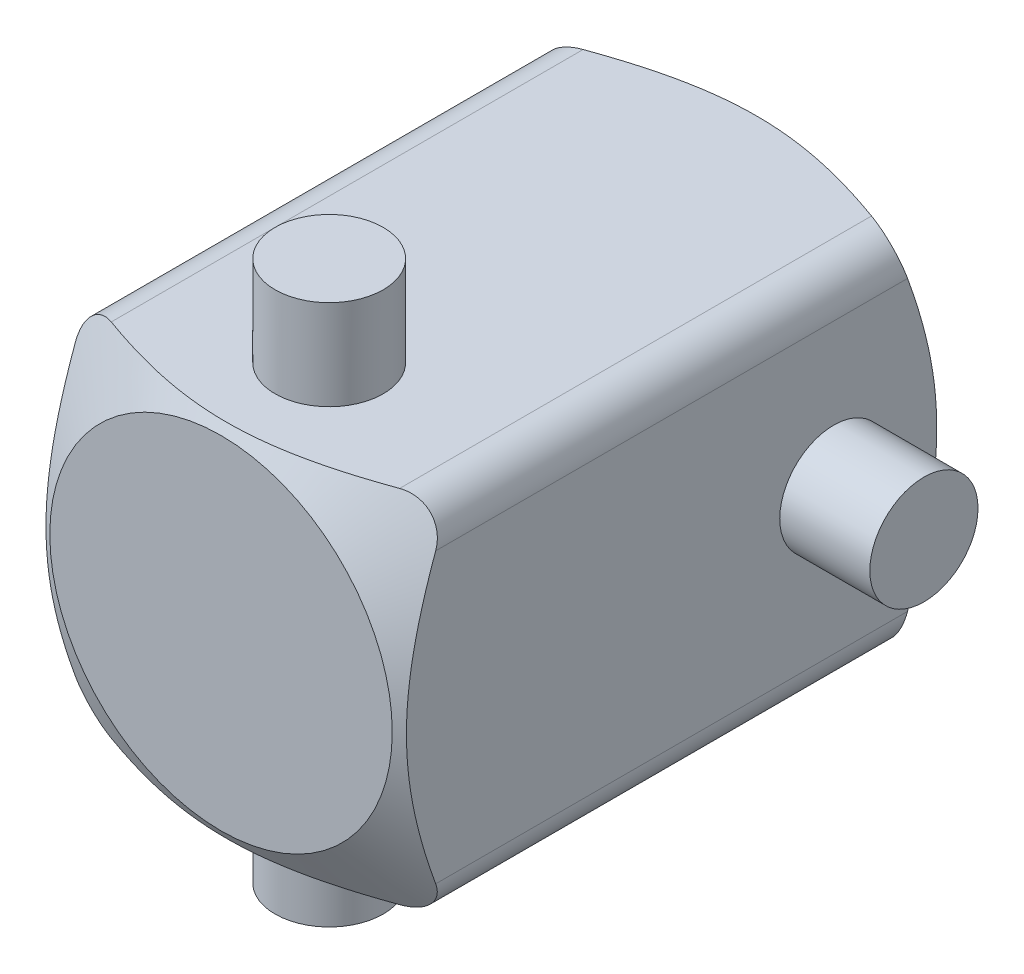
SolidWorks part; units mm, degrees
ref_plane "Alzado" through (0, 0, 0) normal (0, 0, 1) x (1, 0, 0)
ref_plane "Planta" through (0, 0, 0) normal (0, 1, 0) x (1, 0, 0)
ref_plane "Vista lateral" through (0, 0, 0) normal (1, 0, 0) x (0, 0, -1)
sketch "Croquis1" plane through (0, 0, 0) normal (0, 0, 1) x (1, 0, 0)
  line L1 (-5, 5) -> (5, 5)
  line L2 (-5, 5) -> (-5, -5)
  line L3 (-5, -5) -> (5, -5)
  line L4 (5, 5) -> (5, -5)
  line L5 (-5, 5) -> (5, -5) construction
  line L6 (-5, -5) -> (5, 5) construction
  point P0 (0, 0)
  dimension "D1" = 10
  dimension "D2" = 10
extrude "Saliente-Extruir1" add sketch "Croquis1" along normal blind 15
ref_axis "Eje1" through (0, 0, -0.75) along (0, 0, 1)
sketch "Croquis3" plane through (0, 0, 0) normal (1, 0, 0) x (0, 0, -1)
  line L0 (-15, 4.75) -> (-15, 15.04)
  line L1 (-15, -5) -> (-15, 5) construction
  line L2 (-15, 15.04) -> (0, 15.04)
  line L3 (0, 15.04) -> (0, 4.75)
  line L4 (0, -5) -> (0, 5) construction
  line L5 (0, 4.75) -> (-4.4745, 12.5)
  line L6 (-4.4745, 12.5) -> (-10.5255, 12.5)
  line L7 (-10.5255, 12.5) -> (-15, 4.75)
  line L8 (-15, 5) -> (0, 5) construction
  dimension "D1" = 0.25
  dimension "D2" = 0.25
  dimension "D3" = 2.54
  dimension "D4" = 30
  dimension "D5" = 30
  dimension "D6" = 7.5
revolve "Cortar-Revolución1" cut sketch "Croquis3" angle 360 about axis through (0, 0, -0.75) along (0, 0, 1)
fillet "Redondeo1" radius 1 4 edges at (-5, 5, 7.5) (-5, -5, 7.5) (5, -5, 7.5) (5, 5, 7.5)
sketch "Croquis4" plane through (0, 0, 0) normal (1, 0, 0) x (0, 0, -1)
  line L0 (0, -4.75) -> (0, 4.75) construction
  line L1 (0.75, 0) -> (-15.75, 0) construction
  circle A0 centre (-3, 0) radius 1.5
  point P4 (0, 0)
  dimension "D1" = 3
  dimension "D2" = 3
extrude "Saliente-Extruir2" add sketch "Croquis4" along normal mid plane 15
sketch "Croquis5" plane through (0, 0, 0) normal (0, 1, 0) x (1, 0, 0)
  line L0 (0, 0.75) -> (0, -15.75) construction
  line L1 (-4.75, -15) -> (4.75, -15) construction
  circle A0 centre (0, -12) radius 1.5
  dimension "D1" = 3
  dimension "D2" = 3
extrude "Saliente-Extruir3" add sketch "Croquis5" along normal mid plane 15
